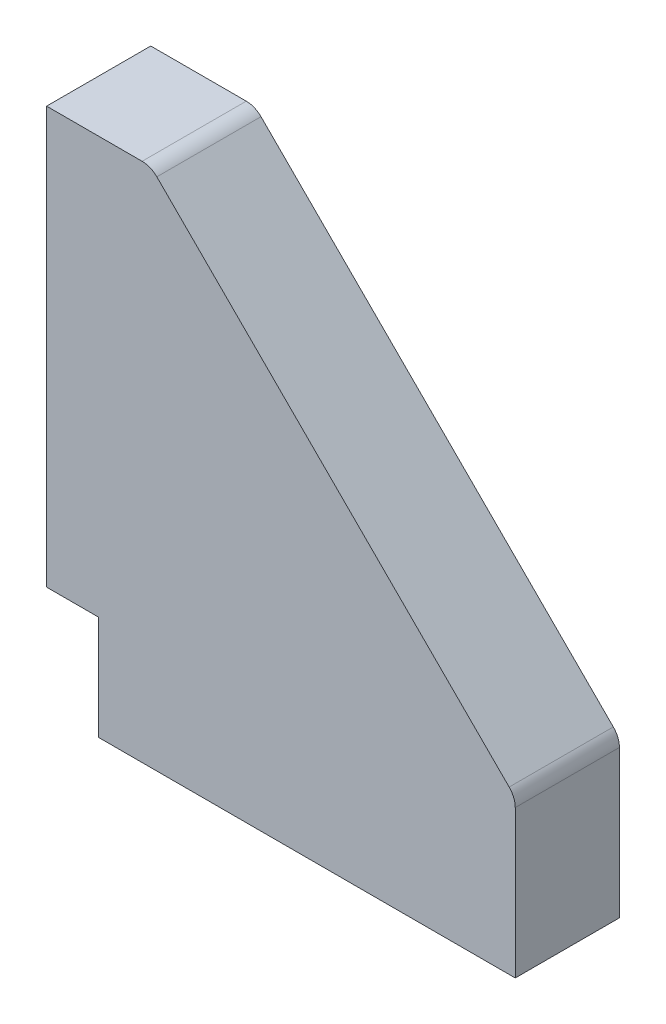
SolidWorks part; units mm, degrees
material "1060 Alloy"
ref_plane "Front Plane" through (0, 0, 0) normal (0, 0, 1) x (1, 0, 0)
ref_plane "Top Plane" through (0, 0, 0) normal (0, 1, 0) x (1, 0, 0)
ref_plane "Right Plane" through (0, 0, 0) normal (1, 0, 0) x (0, 0, -1)
sketch "Sketch1" plane through (0, 0, 0) normal (0, 0, 1) x (1, 0, 0)
  line L0 (0, 0) -> (0, 50.8)
  line L1 (0, 50.8) -> (6.35, 50.8)
  line L2 (6.35, 50.8) -> (50.8, 6.35)
  line L3 (50.8, 6.35) -> (50.8, 0)
  line L4 (50.8, 0) -> (0, 0)
  dimension "D1" = 50.8
  dimension "D2" = 50.8
  dimension "D3" = 6.35
  dimension "D4" = 6.35
extrude "Boss-Extrude1" add sketch "Sketch1" along normal blind 12.7
fillet "Fillet1" radius 2.54 2 edges at (50.8, 6.35, 6.35) (6.35, 50.8, 6.35)
sketch "Sketch2" plane through (0, 0, 0) normal (-1, 0, 0) x (0, 0, 1)
  line L0 (6.3853, 6.35) -> (6.3853, 44.45) construction
  line L1 (12.7, 0) -> (0, 0) construction
  circle A0 centre (6.3853, 44.45) radius 3.175
  circle A1 centre (6.3853, 6.35) radius 3.175
  dimension "D2" = 6.35
  dimension "D1" = 38.1
  dimension "D3" = 6.35
extrude "Cut-Extrude1" cut sketch "Sketch2" against normal blind 7.62
ref_plane "Plane1" through (0, 0, 0) normal (0.7071, -0.7071, 0) x (-0.7071, -0.7071, 0)
mirror "Mirror1" about plane through (0, 0, 0) normal (0.7071, -0.7071, 0) of "Cut-Extrude1"
sketch "Sketch3" plane through (0, 0, 0) normal (0, -1, 0) x (1, 0, 0)
  line L4 (0, 0) -> (50.8, 0)
  line L5 (50.8, 0) -> (50.8, 12.7)
  line L6 (50.8, 12.7) -> (0, 12.7)
  line L7 (0, 12.7) -> (0, 0)
  line L8 (0, 0) -> (50.8, 0)
  line L9 (50.8, 0) -> (50.8, 12.7)
  line L10 (50.8, 12.7) -> (0, 12.7)
  line L11 (0, 12.7) -> (0, 0)
  circle A0 centre (6.35, 6.3853) radius 3.175 construction
  circle A1 centre (44.45, 6.3853) radius 3.175 construction
  circle A2 centre (6.35, 6.3853) radius 3.175
  circle A3 centre (44.45, 6.3853) radius 3.175
  circle M5 centre (44.45, 6.3853) radius 3.175
  circle M6 centre (6.35, 6.3853) radius 3.175
  line M7 (0, 0) -> (50.8, 0)
  line M8 (50.8, 0) -> (50.8, 12.7)
  line M9 (50.8, 12.7) -> (0, 12.7)
  line M10 (0, 12.7) -> (0, 0)
  dimension "D1" = 0
extrude "Boss-Extrude2" add sketch "Sketch3" along normal blind 12.7 contours M10 M7 M8 M9 M6 M5 region at (25.4, 0, 6.3462)
sketch "Sketch4" plane through (0, 0, 0) normal (-1, 0, 0) x (0, 0, 1)
  line L0 (12.7, 50.8) -> (12.7, -12.7) construction
  line L1 (0, 50.8) -> (12.7, 50.8)
  line L2 (0, 50.8) -> (0, 0)
  line L3 (0, 0) -> (12.7, 0)
  line L4 (12.7, 50.8) -> (12.7, 0)
  circle A0 centre (6.3853, 44.45) radius 3.175
  circle A1 centre (6.3853, 6.35) radius 3.175
extrude "Boss-Extrude3" add sketch "Sketch4" along normal blind 6.35
